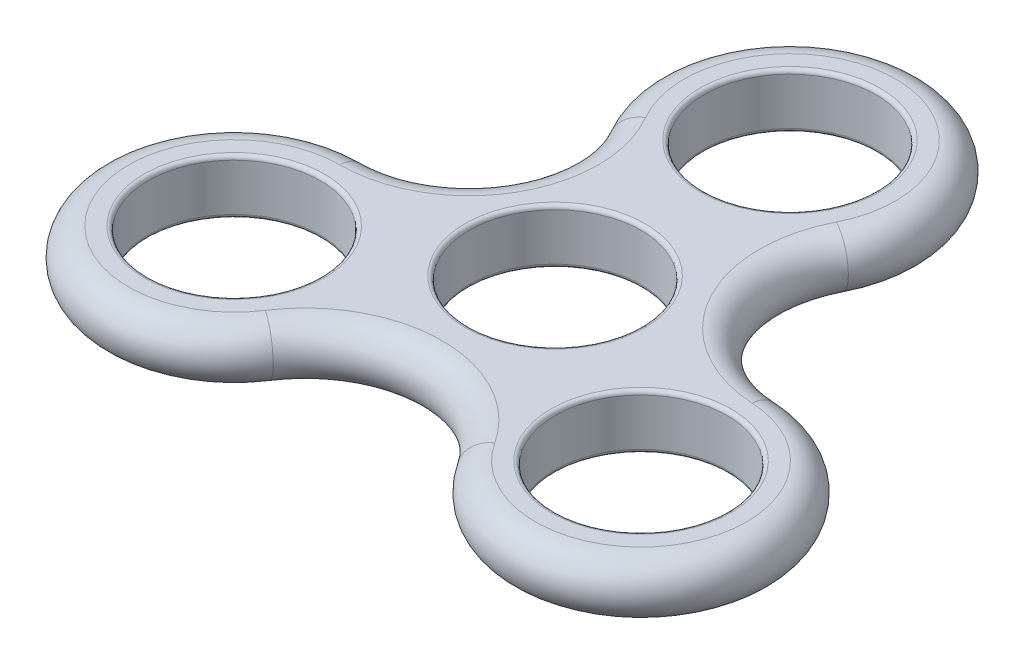
SolidWorks part; units mm, degrees
ref_plane "Front Plane" through (0, 0, 0) normal (0, 0, 1) x (1, 0, 0)
ref_plane "Top Plane" through (0, 0, 0) normal (0, 1, 0) x (1, 0, 0)
ref_plane "Right Plane" through (0, 0, 0) normal (1, 0, 0) x (0, 0, -1)
sketch "Sketch1" plane through (0, 0, 0) normal (0, 1, 0) x (1, 0, 0)
  line L0 (0, 30) -> (0, 0) construction
  circle A0 centre (0, 0) radius 11
  circle A1 centre (0, 30) radius 11
  circle A2 centre (25.9808, -15) radius 11
  circle A3 centre (-25.9808, -15) radius 11
  circle A4 centre (0, 30) radius 17
  circle A5 centre (-25.9808, -15) radius 17
  circle A6 centre (25.9808, -15) radius 17
  arc A7 (-11.7332, -24.2741) -> (11.7332, -24.2741) centre (0, -31.9115) cw
  arc A8 (-14.7224, 21.5) -> (-25.9808, 2) centre (-25.9808, 15) cw
  arc A9 (15.1553, 22.2983) -> (26.8886, 1.9757) centre (27.6362, 15.9558) ccw
  point P24 (28.5558, 0.7914)
  dimension "D1" = 22
  dimension "D2" = 30
  dimension "D6" = 13
  dimension "D7" = 14
  dimension "D8" = 14
  dimension "D4" = 25.9808
  dimension "D5" = 6
  dimension "D3" = 3
extrude "Boss-Extrude1" add sketch "Sketch1" along normal mid plane 7 contours A1 A4 | A6 A2 | A9 A4 A0 A8 A5 A7 A6 | A5 A3 region at (16.0648, 0, -26.1522) region at (0.4729, 0, -12.3017) region at (-14.2999, 0, 3.3192) region at (37.9694, 0, 3.6353)
fillet "Fillet1" 2 edges at (-0.4541, 3.5, -46.9939) (-0.4541, -3.5, -46.9939) type full round first side face at (0.0189, 3.5, 0.0109) second side face at (0.0189, -3.5, 0.0109) middle face at (-0.1188, 0, -34.4465)
fillet "Fillet2" radius 0.5 8 edges at (0, -3.5, 11) (0, 3.5, 11) (25.9808, -3.5, 26) (25.9808, 3.5, 26) (-25.9808, -3.5, 26) (-25.9808, 3.5, 26) (0, -3.5, -19) (0, 3.5, -19)
